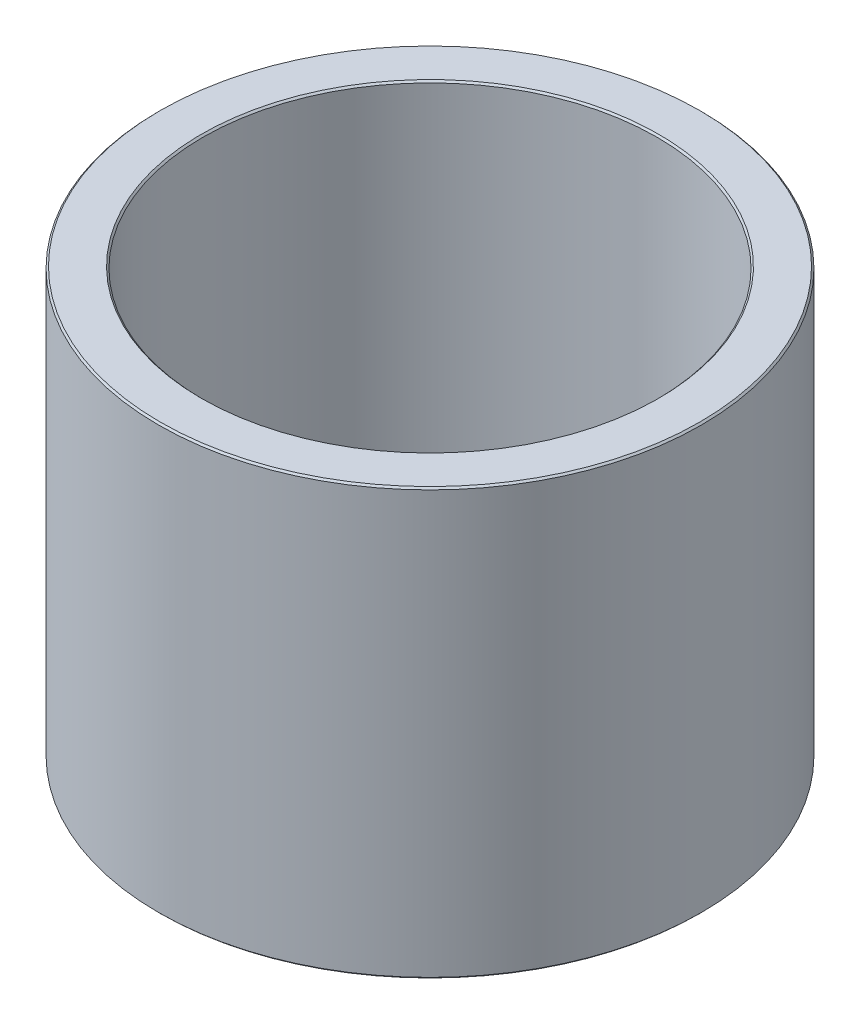
SolidWorks part; units mm, degrees
ref_plane "Front Plane" through (0, 0, 0) normal (0, 0, 1) x (1, 0, 0)
ref_plane "Top Plane" through (0, 0, 0) normal (0, 1, 0) x (1, 0, 0)
ref_plane "Right Plane" through (0, 0, 0) normal (1, 0, 0) x (0, 0, -1)
sketch "Sketch1" plane through (0, 0, 0) normal (0, 1, 0) x (1, 0, 0)
  circle A0 centre (0, 0) radius 50
  dimension "SLEEVE_OD" = 100
extrude "Boss-Extrude1" add sketch "Sketch1" along normal blind 78.3762
sketch "Sketch2" plane through (0, 0, 0) normal (0, 1, 0) x (1, 0, 0)
  circle A0 centre (0, 0) radius 41.811
  dimension "BORE_D" = 83.622
extrude "Cut-Extrude1" cut sketch "Sketch2" along normal through all
chamfer "Chamfer1" distance 0.3124 angle 45 4 edges at (0, 78.3762, 41.811) (0, 0, 41.811) (0, 0, 50) (0, 78.3762, 50)
